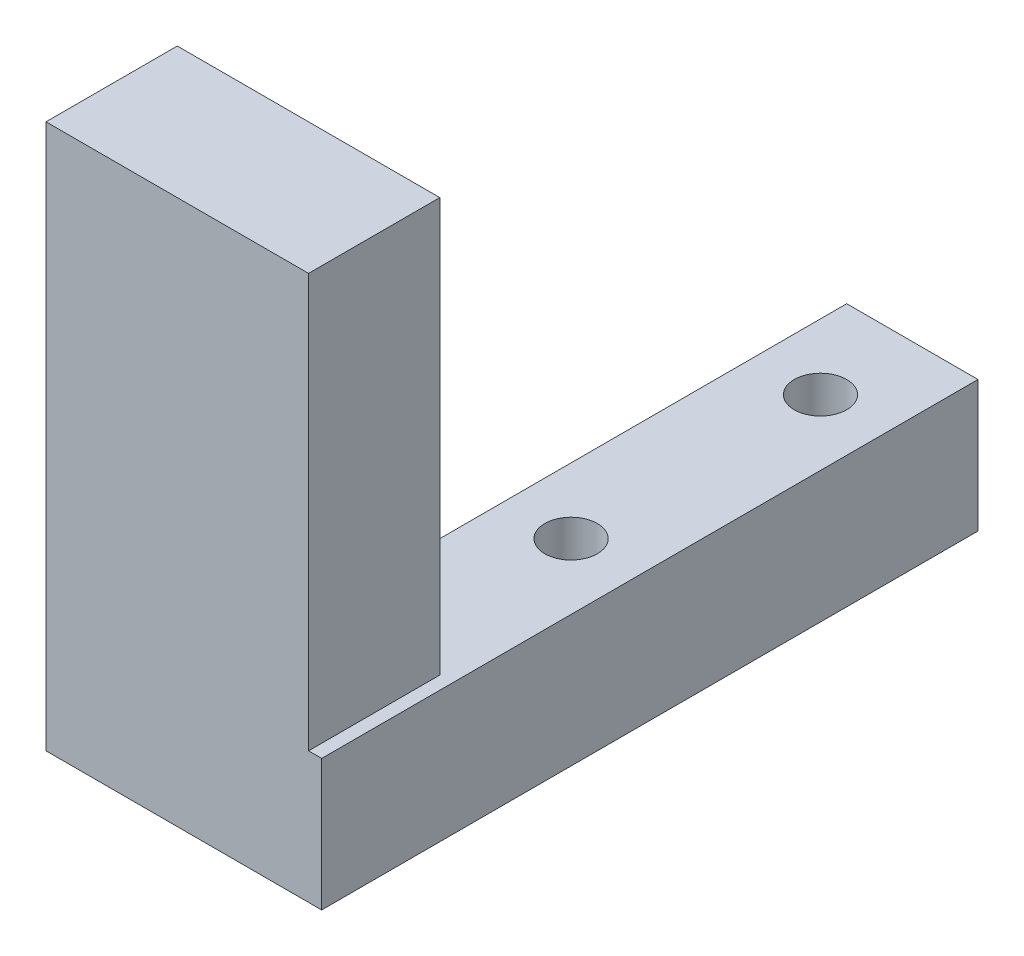
SolidWorks part; units mm, degrees
ref_plane "Front Plane" through (0, 0, 0) normal (0, 0, 1) x (1, 0, 0)
ref_plane "Top Plane" through (0, 0, 0) normal (0, 1, 0) x (1, 0, 0)
ref_plane "Right Plane" through (0, 0, 0) normal (1, 0, 0) x (0, 0, -1)
sketch "Sketch1" plane through (0, 0, 0) normal (0, 0, 1) x (1, 0, 0)
  line L1 (-7.8513, 3.6433) -> (2.1487, 3.6433)
  line L2 (-7.8513, 3.6433) -> (-7.8513, -6.3567)
  line L3 (-7.8513, -6.3567) -> (2.1487, -6.3567)
  line L4 (2.1487, 3.6433) -> (2.1487, -6.3567)
  dimension "D1" = 10
  dimension "D2" = 10
extrude "Boss-Extrude1" add sketch "Sketch1" along normal blind 50
sketch "Sketch3" plane through (-7.8513, 0, 0) normal (-1, 0, 0) x (0, 0, 1)
  line L0 (50, -6.3567) -> (0, -6.3567) construction
  line L1 (50, 3.6433) -> (40, 3.6433)
  line L2 (50, 3.6433) -> (50, -6.3567)
  line L3 (50, -6.3567) -> (40, -6.3567)
  line L4 (40, 3.6433) -> (40, -6.3567)
  dimension "D1" = 10
  dimension "D2" = 10
extrude "Boss-Extrude3" add sketch "Sketch3" along normal blind 11
sketch "Sketch8" plane through (0, 3.6433, 0) normal (0, 1, 0) x (1, 0, 0)
  line L1 (-18.8513, -50) -> (1.1487, -50)
  line L2 (-18.8513, -50) -> (-18.8513, -40)
  line L3 (-18.8513, -40) -> (1.1487, -40)
  line L4 (1.1487, -50) -> (1.1487, -40)
  dimension "D1" = 20
extrude "Boss-Extrude4" add sketch "Sketch8" along normal blind 23
sketch "Sketch9" plane through (0, 3.6433, 0) normal (0, 1, 0) x (1, 0, 0)
  line L0 (-2.8513, 0) -> (-2.8513, -5)
  line L3 (2.1487, 0) -> (-7.8513, 0) construction
  line L4 (-2.8513, -5) -> (-2.8513, -7)
  line L5 (-2.8513, -9) -> (-2.8513, -24)
  line L6 (-2.8513, -24) -> (-2.8513, -26)
  line L7 (2.1487, -50) -> (2.1487, 0) construction
  circle A0 centre (-2.8513, -7) radius 2
  circle A1 centre (-2.8513, -26) radius 2
  dimension "D1" = 5
  dimension "D3" = 15
  dimension "D2" = 2
  dimension "D4" = 2
extrude "Cut-Extrude2" cut sketch "Sketch9" against normal blind 23 contours A0
extrude "Cut-Extrude3" cut sketch "Sketch9<4>" against normal blind 23 contours A1
sketch "Sketch9<4>" plane through (0, 3.6433, 0) normal (0, 1, 0) x (1, 0, 0) same geometry as "Sketch9"
extrude "Boss-Extrude5" add sketch "Sketch8<4>" along normal blind 31
sketch "Sketch8<4>" plane through (0, 3.6433, 0) normal (0, 1, 0) x (1, 0, 0) same geometry as "Sketch8"
extrude "Boss-Extrude6" add sketch "Sketch8<5>" along normal blind 31.5
sketch "Sketch8<5>" plane through (0, 3.6433, 0) normal (0, 1, 0) x (1, 0, 0) same geometry as "Sketch8"
sketch "草图1" plane through (0, -6.3567, 0) normal (0, -1, 0) x (1, 0, 0)
  line L0 (-2.8513, 26) -> (-7.8513, 26) construction
  line L1 (-7.8513, 40) -> (-7.8513, 0) construction
  line L2 (-2.8513, 26) -> (2.1487, 26)
  line L3 (2.1487, 50) -> (2.1487, 0) construction
  circle A0 centre (-2.8513, 7) radius 2 construction
  circle A1 centre (-2.8513, 26) radius 2 construction
  circle A2 centre (-2.8513, 7) radius 2 construction
  circle A3 centre (-2.8513, 26) radius 2 construction
  point P10 (-7.8513, 26)
